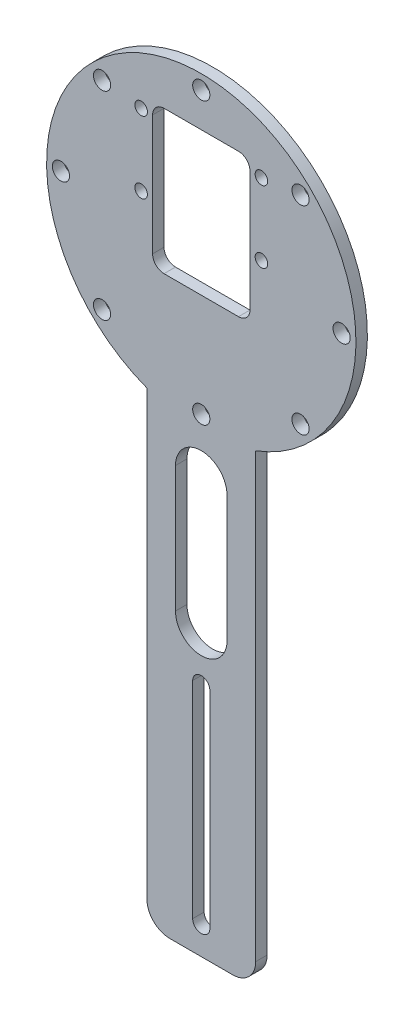
SolidWorks part; units mm, degrees
material "Epoxy, renforcé"
ref_plane "Plan de face" through (0, 0, 0) normal (0, 0, 1) x (1, 0, 0)
ref_plane "Plan de dessus" through (0, 0, 0) normal (0, 1, 0) x (1, 0, 0)
ref_plane "Plan de droite" through (0, 0, 0) normal (1, 0, 0) x (0, 0, -1)
sketch "Esquisse1" plane through (0, 0, 0) normal (0, 0, 1) x (1, 0, 0)
  line L0 (0, 0) -> (0, 100) construction
  line L1 (0, 0) -> (-9.5, 0) construction
  line L2 (9.5, 0) -> (-9.5, 0)
  line L3 (0, 100) -> (0, 133.5) construction
  line L4 (-8.5, 125) -> (8.5, 125)
  line L5 (8.5, 100) -> (-8.5, 100)
  line L6 (-8.5, 100) -> (-8.5, 125)
  line L13 (8.5, 100) -> (8.5, 125)
  line L17 (-10.5, 110.5) -> (-10.5, 123) construction
  line L19 (-9.5, 81.2265) -> (-9.5, 0)
  line L20 (9.5, 81.2265) -> (9.5, 0)
  circle A0 centre (-10.5, 123) radius 1.1
  circle A1 centre (-10.5, 110.5) radius 1.1
  circle A2 centre (10.5, 110.5) radius 1.1
  circle A3 centre (10.5, 123) radius 1.1
  arc A4 (9.5, 81.2265) -> (-9.5, 81.2265) centre (0, 106.5) ccw
  circle A5 centre (0, 131) radius 1.5
  circle A6 centre (17.3241, 123.8241) radius 1.5
  circle A7 centre (24.5, 106.5) radius 1.5
  circle A8 centre (17.3241, 89.1759) radius 1.5
  circle A9 centre (0, 82) radius 1.5
  circle A10 centre (-17.3241, 89.1759) radius 1.5
  circle A11 centre (-24.5, 106.5) radius 1.5
  circle A12 centre (-17.3241, 123.8241) radius 1.5
  point P31 (0, 0)
  point P40 (0, 106.5)
  dimension "D4" = 2.2
  dimension "D9" = 2.2
  dimension "D12" = 54
  dimension "D11" = 3
  dimension "D2" = 100
  dimension "D3" = 2
  dimension "D5" = 2
  dimension "D6" = 12.5
  dimension "D7" = 25
  dimension "D8" = 19
  dimension "D10" = 6.5
  dimension "D13" = 2.5
  dimension "D14" = 17
  dimension "D15" = 8
extrude "Boss.-Extru.1" add sketch "Esquisse1" along normal blind 2
fillet "Congé1" radius 2 4 edges at (-8.5, 100, 1) (8.5, 100, 1) (8.5, 125, 1) (-8.5, 125, 1)
sketch "Esquisse2" plane through (0, 0, 2) normal (0, 0, 1) x (1, 0, 0)
  line L0 (0, 72) -> (0, 50) construction
  line L1 (4.5, 72) -> (4.5, 50)
  line L2 (-4.5, 72) -> (-4.5, 50)
  line L3 (9.5, 0) -> (9.5, 81.2265) construction
  line L4 (6.5, 100) -> (-6.5, 100) construction
  line L6 (-9.5, 0) -> (9.5, 0) construction
  line L7 (0, 41) -> (0, 5) construction
  line L8 (1.5, 41) -> (1.5, 5)
  line L9 (-1.5, 41) -> (-1.5, 5)
  arc A0 (4.5, 72) -> (-4.5, 72) centre (0, 72) ccw
  arc A1 (-4.5, 50) -> (4.5, 50) centre (0, 50) ccw
  arc A2 (1.5, 41) -> (-1.5, 41) centre (0, 41) ccw
  arc A3 (-1.5, 5) -> (1.5, 5) centre (0, 5) ccw
  point P3 (0, 61)
  point P12 (0, 100)
  point P17 (0, 23)
  point P22 (0, 0)
  point P23 (0, 36.1078)
  dimension "D1" = 5
  dimension "D2" = 28
  dimension "D3" = 50
  dimension "D4" = 1.5
  dimension "D5" = 36
  dimension "D6" = 5
extrude "Enlèv. mat.-Extru.1" cut sketch "Esquisse2" against normal blind 2
fillet "Congé2" radius 4 2 edges at (-9.5, 0, 1) (9.5, 0, 1)
